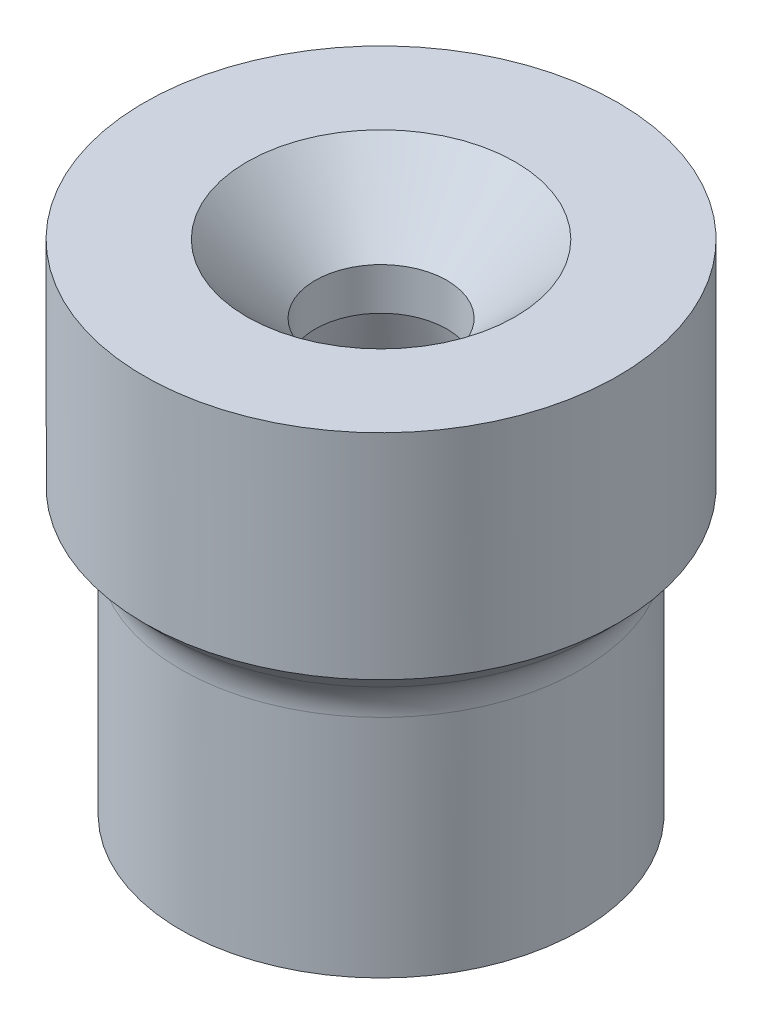
SolidWorks part; units mm, degrees
material "C (Grafite)"
ref_plane "Piano frontale" through (0, 0, 0) normal (0, 0, 1) x (1, 0, 0)
ref_plane "Piano superiore" through (0, 0, 0) normal (0, 1, 0) x (1, 0, 0)
ref_plane "Piano destro" through (0, 0, 0) normal (1, 0, 0) x (0, 0, -1)
sketch "Schizzo1" plane through (0, 0, 0) normal (0, 0, 1) x (1, 0, 0)
  line L0 (0, 0) -> (0, 63.7736) construction
  line L1 (-32.2345, 0) -> (-12.5, 73.6501)
  line L2 (-12.5, 73.6501) -> (-12.5, 81.6501)
  line L3 (-12.5, 81.6501) -> (-25.4904, 94.6405)
  line L4 (-25.4904, 94.6405) -> (-63, 94.6405)
  line L15 (-38, 64.6405) -> (-38, 0)
  line L16 (-38, 0) -> (-32.2345, 0)
  line L17 (-38, 64.6405) -> (-63, 94.6405)
  dimension "D1" = 25
  dimension "D2" = 64.469
  dimension "D6" = 76
  dimension "D9" = 8
  dimension "D3" = 15
  dimension "D4" = 94.6405
  dimension "D10" = 45
  dimension "D5" = 126
  dimension "D7" = 30
revolve "Rivoluzione1" add sketch "Schizzo1" angle 360 about L0 region at (-31.8764, 60.9329, 0)
sketch "Schizzo4" plane through (0, 0, 0) normal (0, 0, 1) x (1, 0, 0)
  line L0 (-38, 64.6405) -> (-38, 94.6405)
  line L1 (-25.4904, 94.6405) -> (-63, 94.6405) construction
  line L2 (-38, 94.6405) -> (-63, 94.6405)
  line L3 (-63, 94.6405) -> (-63, 64.6405)
  line L4 (-63, 64.6405) -> (-38, 64.6405)
  line L5 (-38, 64.6405) -> (-38, 0) construction
revolve "Taglia-Rivoluzione3" cut sketch "Schizzo4" angle 360 about L0
sketch "Schizzo5" plane through (0, 0, 0) normal (0, 0, 1) x (1, 0, 0)
  line L0 (-38, 94.6405) -> (-45, 94.6405)
  line L1 (-38, 64.6405) -> (-38, 0) construction
  line L2 (-45, 94.6405) -> (-45, 54)
  line L3 (-45, 54) -> (-38, 54)
  line L4 (-25.4904, 94.6405) -> (-63, 94.6405) construction
  line L5 (0, 0) -> (0, 63.7736) construction
  line L6 (-38, 0) -> (-32.2345, 0) construction
  line L7 (-38, 54) -> (-38, 94.6405)
  line L9 (-45, 54) -> (-38, 47)
  line L10 (-38, 94.6405) -> (-38, 0) construction
  line L12 (-38, 54) -> (-38, 47)
  dimension "D1" = 7
  dimension "D2" = 90
  dimension "D3" = 54
revolve "Rivoluzione2" add sketch "Schizzo5" angle 360 about L5 region at (-41.5, 74.3203, 0) region at (-40.3333, 51.6667, 0)
fillet "Raccordo1" radius 10 1 edges at (0, 47, 38)
fillet "Raccordo2" [suppressed] radius 10
equation "\"epsilon\"= 6.65"
equation "\"D2@Schizzo1\"= sqr ( \"epsilon\" ) * \"D1@Schizzo1\""
